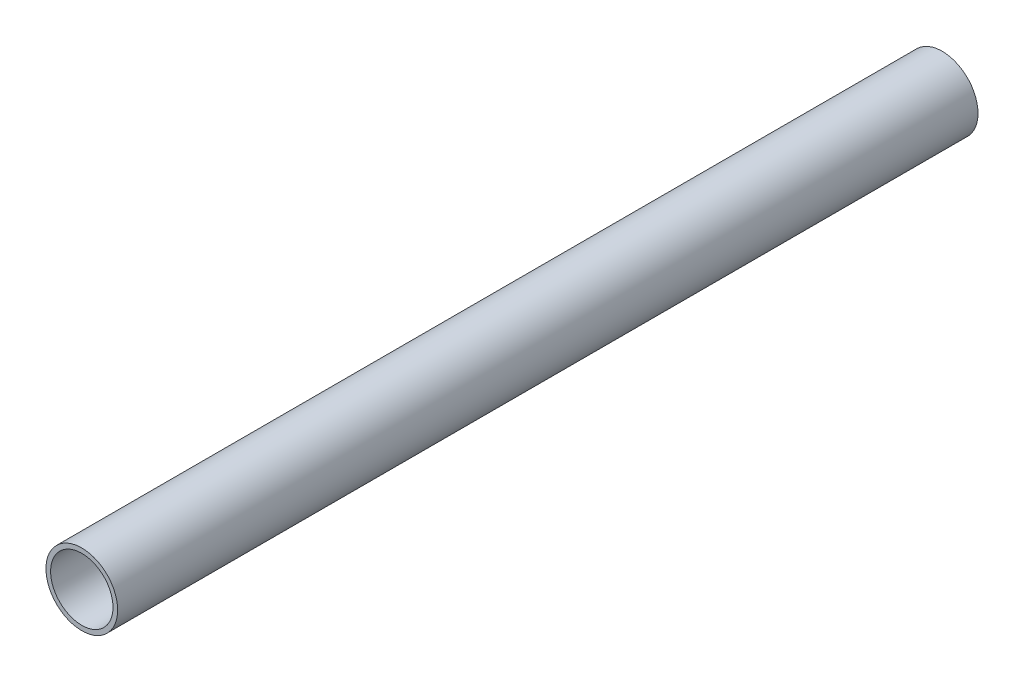
SolidWorks part; units mm, degrees
ref_plane "Front Plane" through (0, 0, 0) normal (0, 0, 1) x (1, 0, 0)
ref_plane "Top Plane" through (0, 0, 0) normal (0, 1, 0) x (1, 0, 0)
ref_plane "Right Plane" through (0, 0, 0) normal (1, 0, 0) x (0, 0, -1)
sketch "Sketch1" plane through (0, 0, 0) normal (0, 0, 1) x (1, 0, 0)
  line L0 (12.7, 0) -> (11.049, 0) construction
  line L1 (-12.7, 0) -> (12.7, 0) construction
  dimension "OD" = 25.4
  dimension "Wall Thickness" = 1.651
sketch "Sketch2" plane through (0, 0, 0) normal (1, 0, 0) x (0, 0, -1)
  line L0 (304.8, 0) -> (-304.8, 0)
  point P4 (0, 0)
  dimension "Length" = 609.6
sketch "Sketch3" plane through (0, 0, 0) normal (0, 0, 1) x (1, 0, 0)
  circle A0 centre (0, 0) radius 12.7
  circle A1 centre (0, 0) radius 11.049
extrude "Boss-Extrude1" add sketch "Sketch3" along normal up to vertex (304.8 mm away) up to point (0, 0, 304.8)
